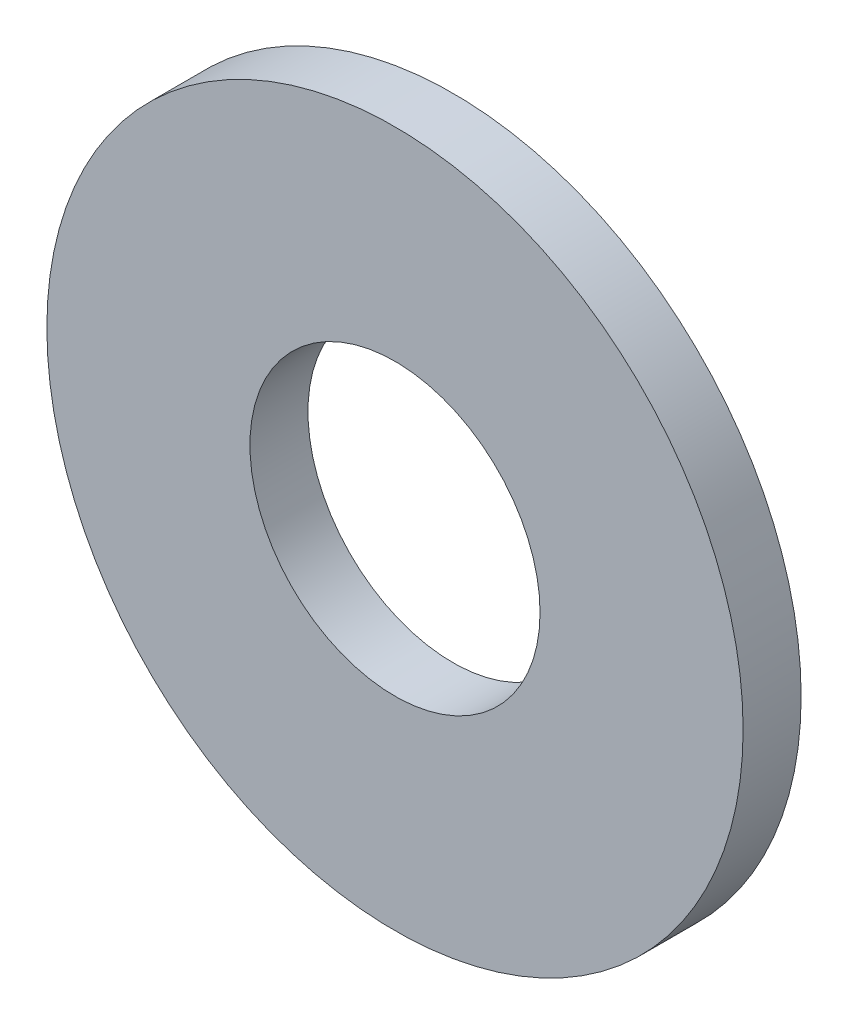
SolidWorks part; units mm, degrees
material "6061-T6 (SS)"
ref_plane "Alzado" through (0, 0, 0) normal (0, 0, 1) x (1, 0, 0)
ref_plane "Planta" through (0, 0, 0) normal (0, 1, 0) x (1, 0, 0)
ref_plane "Vista lateral" through (0, 0, 0) normal (1, 0, 0) x (0, 0, -1)
sketch3d "Sk_Anillo"
  line L0 (-425.1, 65, 58) -> (-425.1, 65, 60)
sweep "Anillo" add path "Sk_Anillo" circular profile diameter 24 parameters "D3"=24
sketch3d "Sk_Taladro"
  line L0 (-425.1, 65, 58) -> (-425.1, 65, 60)
sweep "Taladro" cut path "Sk_Taladro" circular profile diameter 10 parameters "D3"=10
